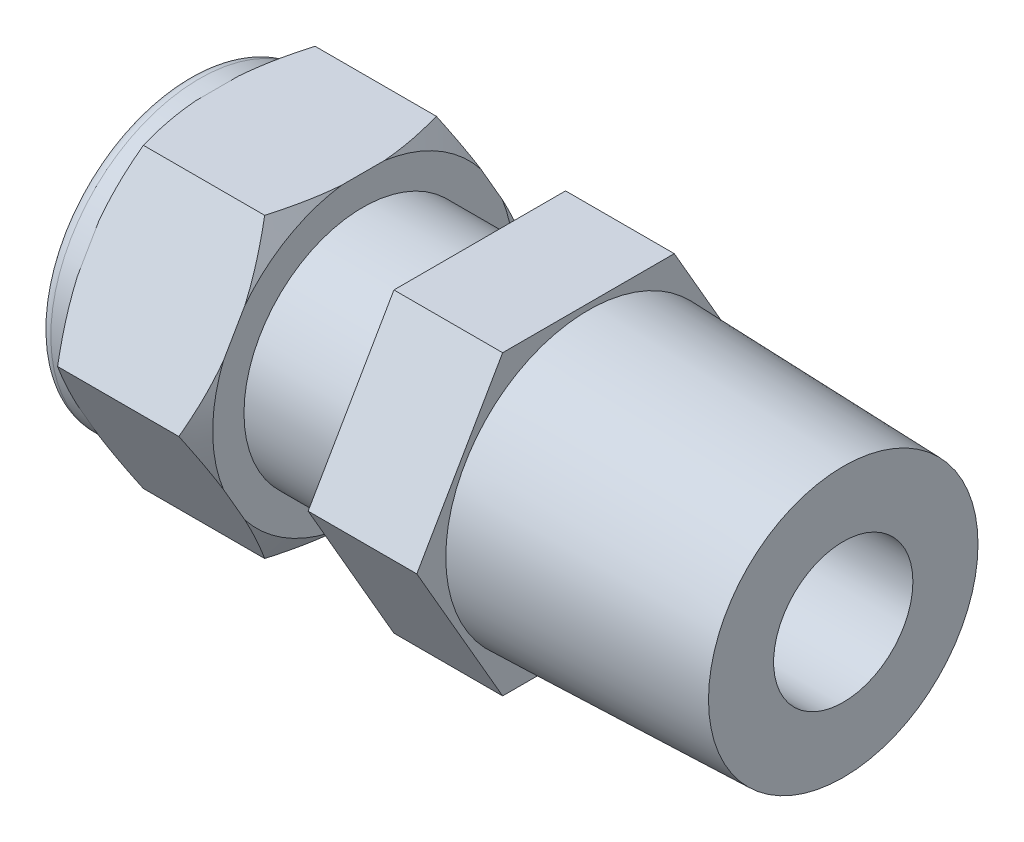
SolidWorks part; units mm, degrees
ref_plane "Front" through (0, 0, 0) normal (0, 0, 1) x (1, 0, 0)
ref_plane "Top" through (0, 0, 0) normal (0, 1, 0) x (1, 0, 0)
ref_plane "Right" through (0, 0, 0) normal (1, 0, 0) x (0, 0, -1)
sketch "BodySch" plane through (0, 0, 0) normal (0, 0, 1) x (1, 0, 0)
  line L0 (-103.6847, 0) -> (134.0726, 0) construction
  line L1 (-49.022, 0) -> (-49.022, 11.1125)
  line L2 (-49.022, 11.1125) -> (-41.3766, 11.1125)
  line L3 (-41.3766, 11.1125) -> (-41.3766, 8.89)
  line L4 (-41.3766, 8.89) -> (-27.178, 8.89)
  line L5 (-27.178, 8.89) -> (-27.178, 10.668)
  line L6 (-27.178, 10.668) -> (-19.05, 10.668)
  line L8 (-19.05, 10.668) -> (0, 10.0749)
  line L9 (0, 10.0749) -> (0, 0)
  line L14 (0, 0) -> (-49.022, 0)
  dimension "D4" = 1.783
revolve "Body" add sketch "BodySch" angle 360 about L0
sketch "Hex1Sch_G" plane through (-41.3766, 0, 0) normal (1, 0, 0) x (0, 0, -1)
  line L1 (12.8316, 0) -> (6.4158, 11.1125)
  line L2 (6.4158, 11.1125) -> (-6.4158, 11.1125)
  line L3 (-6.4158, 11.1125) -> (-12.8316, 0)
  line L4 (-12.8316, 0) -> (-6.4158, -11.1125)
  line L5 (-6.4158, -11.1125) -> (6.4158, -11.1125)
  line L6 (6.4158, -11.1125) -> (12.8316, 0)
  circle A0 centre (0, 0) radius 11.1125 construction
  dimension "G" = 22.225
extrude "Hex1" add sketch "Hex1Sch_G" along normal mid plane 10.922
sketch "PlaneCSch" plane through (0, 0, 0) normal (0, 0, 1) x (1, 0, 0)
  line L0 (-27.178, 10.668) -> (-27.178, -10.668) construction
  point P0 (-27.178, 5.1403)
ref_plane "PlaneC" through (-27.178, 0, 0) normal (-1, 0, 0) x (0, 0, 1)
sketch "Hex2Sch_F" plane through (-27.178, 0, 0) normal (-1, 0, 0) x (0, 0, 1)
  line L3 (12.8316, 0) -> (6.4158, 11.1125)
  line L5 (6.4158, 11.1125) -> (-6.4158, 11.1125)
  line L7 (-6.4158, 11.1125) -> (-12.8316, 0)
  line L9 (-12.8316, 0) -> (-6.4158, -11.1125)
  line L11 (-6.4158, -11.1125) -> (6.4158, -11.1125)
  line L12 (6.4158, -11.1125) -> (12.8316, 0)
  circle A2 centre (0, 0) radius 11.1125 construction
  dimension "F" = 22.225
extrude "Hex2" add sketch "Hex2Sch_F" against normal blind 8.128
sketch "HexfilletSch" plane through (0, 0, 0) normal (0, 1, 0) x (1, 0, 0)
  line L0 (-46.8376, 11.2277) -> (-45.9116, 12.8316)
  line L1 (-46.8376, 12.8316) -> (-46.8376, 9.6237) construction
  line L2 (-35.9156, 12.8316) -> (-46.8376, 12.8316) construction
  line L3 (-35.9156, 12.8316) -> (-35.9156, 6.4158) construction
  line L5 (-35.9156, 11.2277) -> (-36.8416, 12.8316)
  line L6 (-46.8376, 11.2277) -> (-46.8376, 12.8316)
  line L7 (-35.9156, 11.2277) -> (-35.9156, 12.8316)
  line L8 (-46.8376, 12.8316) -> (-45.9116, 12.8316)
  line L9 (-41.9948, 0) -> (5.5242, 0) construction
  line L10 (-103.6847, 0) -> (134.0726, 0) construction
  line L12 (-35.9156, 12.8316) -> (-36.8416, 12.8316)
  dimension "D1" = 60
  dimension "D2" = 30
fillet "BodyFillet" radius 0.889 1 edges at (-49.022, 0, 11.1125)
revolve "Hexfillet" cut sketch "HexfilletSch" angle 360 about L9
sketch "DSch" plane through (-49.022, 0, 0) normal (1, 0, 0) x (0, 0, -1)
  circle A0 centre (0, 0) radius 6.35
  dimension "T" = 12.7
extrude "Cut-ExtrudeD" cut sketch "DSch" along normal blind 22.86
sketch "E" plane through (0, 0, 0) normal (1, 0, 0) x (0, 0, -1)
  circle A0 centre (0, 0) radius 5.207
  dimension "E" = 10.414
extrude "Cut-ExtrudeE" cut sketch "E" against normal up to surface (26.162 mm away) up to face at (-26.162, 0, -6.35)
sketch "Sketch1" plane through (0, 0, 0) normal (0, 1, 0) x (1, 0, 0)
  line L0 (0, -5.207) -> (0, 5.207) construction
  line L1 (-19.05, -10.668) -> (-19.05, 10.668) construction
  line L2 (-26.162, 5.207) -> (-26.162, -5.207) construction
  point P0 (0, 0)
  point P4 (-19.05, 0)
  point P7 (-26.162, 0)
other "CPoint1" parameters "Diameter"=12.7, "StubLength"=0
ref_axis "Axis1" through (10, 0, 0) along (-1, 0, 0)
other "RPoint1"
other "CPoint2" parameters "Diameter"=12.7, "StubLength"=0
ref_axis "Axis2" through (-36.162, 0, 0) along (1, 0, 0)
equation "\"Hex1_middle_point@BodySch\"=\"C@BodySch\"*.35"
equation "\"Depth@Hex1\"=\"C@BodySch\"*.5"
equation "\"Depth@Hex2\"=\"Length@BodySch\"-\"L4@BodySch\"-\"C@BodySch\""
equation "\"Dia_ouside_D1@BodySch\"=\"G@Hex1Sch_G\""
equation "\"D1@BodyFillet\"=\"Dia_ouside_D1@BodySch\"/25"
